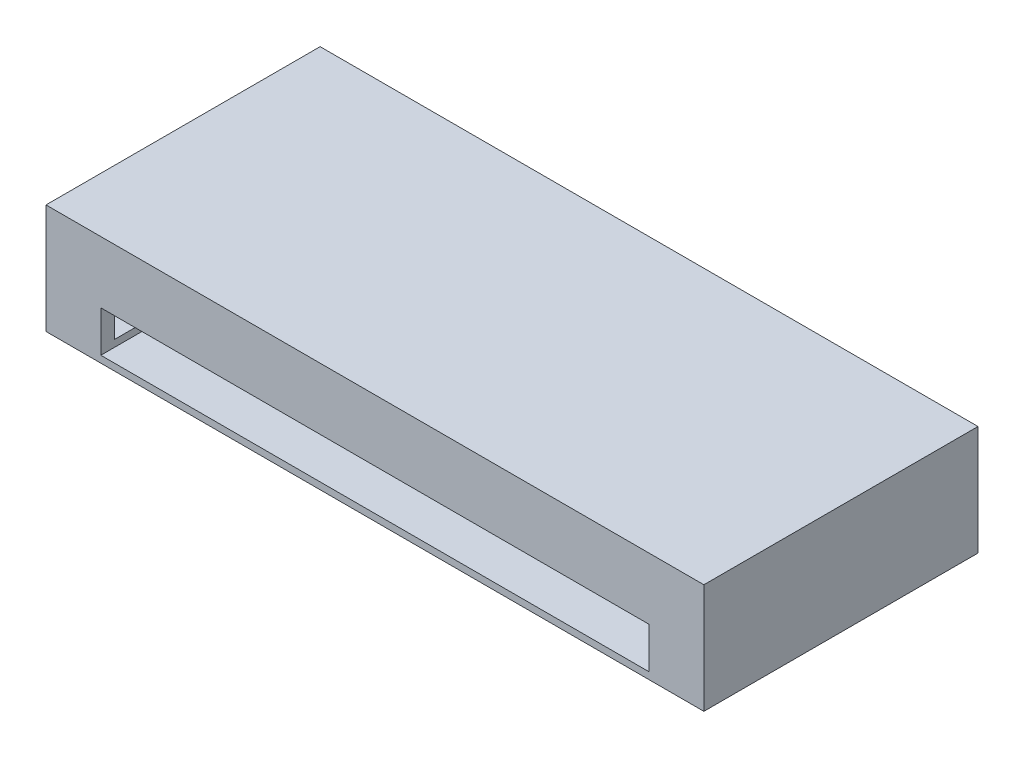
SolidWorks part; units mm, degrees
ref_plane "Front Plane" through (0, 0, 0) normal (0, 0, 1) x (1, 0, 0)
ref_plane "Top Plane" through (0, 0, 0) normal (0, 1, 0) x (1, 0, 0)
ref_plane "Right Plane" through (0, 0, 0) normal (1, 0, 0) x (0, 0, -1)
sketch "Sketch1" plane through (0, 0, 0) normal (0, 1, 0) x (1, 0, 0)
  line L1 (-152.4, -63.5) -> (152.4, -63.5)
  line L2 (-152.4, -63.5) -> (-152.4, 63.5)
  line L3 (-152.4, 63.5) -> (152.4, 63.5)
  line L4 (152.4, -63.5) -> (152.4, 63.5)
  line L5 (-152.4, -63.5) -> (152.4, 63.5) construction
  line L6 (-152.4, 63.5) -> (152.4, -63.5) construction
  point P0 (0, 0)
  dimension "D1" = 304.8
  dimension "D2" = 127
extrude "Boss-Extrude1" add sketch "Sketch1" along normal blind 50.8
shell "Shell1" thickness 6.35
sketch "Sketch2" plane through (0, 0, 63.5) normal (0, 0, 1) x (1, 0, 0)
  line L1 (-127, 3.175) -> (127, 3.175)
  line L2 (-127, 3.175) -> (-127, 22.225)
  line L3 (-127, 22.225) -> (127, 22.225)
  line L4 (127, 3.175) -> (127, 22.225)
  line L5 (-127, 3.175) -> (127, 22.225) construction
  line L6 (-127, 22.225) -> (127, 3.175) construction
  point P0 (0, 12.7)
  dimension "D1" = 254
  dimension "D2" = 19.05
  dimension "D3" = 12.7
extrude "Cut-Extrude1" cut sketch "Sketch2" against normal through all both and the other way through all
